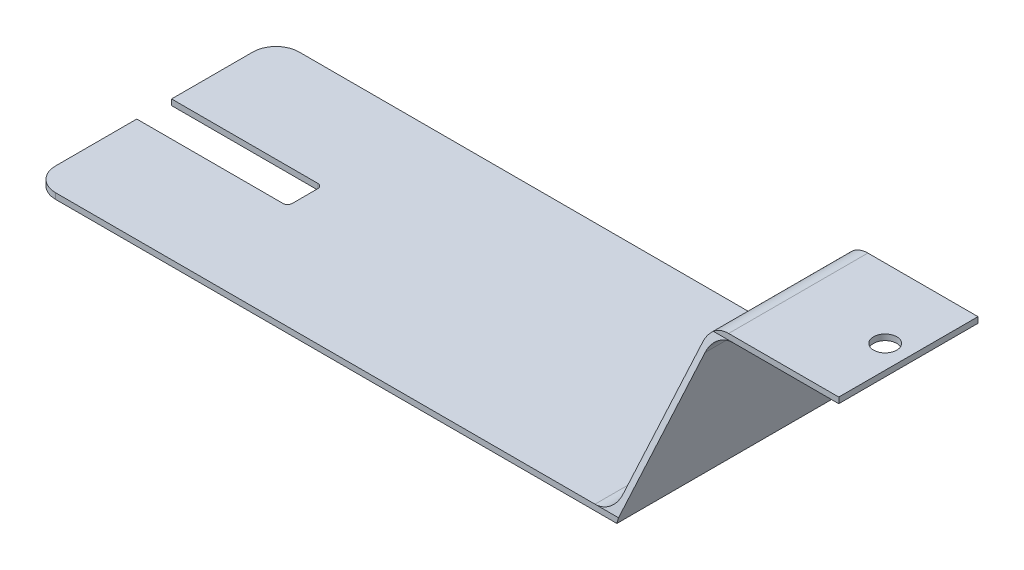
SolidWorks part; units mm, degrees
material "PBT General Purpose"
ref_plane "Front Plane" through (0, 0, 0) normal (0, 0, 1) x (1, 0, 0)
ref_plane "Top Plane" through (0, 0, 0) normal (0, 1, 0) x (1, 0, 0)
ref_plane "Right Plane" through (0, 0, 0) normal (1, 0, 0) x (0, 0, -1)
sketch "Sketch1" plane through (0, 0, 0) normal (0, 0, 1) x (1, 0, 0)
  line L0 (125, 1.25) -> (145, 1.25) construction
  line L1 (-125, -1.25) -> (125, -1.25)
  line L2 (-125, -1.25) -> (-125, 1.25)
  line L3 (-125, 1.25) -> (125, 1.25)
  line L4 (125, -1.25) -> (125, 1.25)
  line L5 (-125, -1.25) -> (125, 1.25) construction
  line L6 (-125, 1.25) -> (125, -1.25) construction
  line L7 (145, 1.25) -> (145, 71.25) construction
  line L8 (125, 1.25) -> (145, 71.25)
  line L9 (146.8858, 68.75) -> (126.8858, -1.25)
  line L10 (125, -1.25) -> (126.8858, -1.25)
  line L11 (145, 71.25) -> (200, 71.25)
  line L12 (200, 71.25) -> (200, 68.75)
  line L13 (200, 68.75) -> (146.8858, 68.75)
  point P0 (0, 0)
  dimension "D1" = 2.5
  dimension "D2" = 250
  dimension "D3" = 20
  dimension "D4" = 70
  dimension "D5" = 2.5
  dimension "D6" = 55
  dimension "D7" = 2.5
extrude "Boss-Extrude1" add sketch "Sketch1" along normal blind 105 contours L1 L10 L9 L13 L12 L11 L8 L3 L2
sketch "Sketch2" plane through (0, 1.25, 0) normal (0, 1, 0) x (1, 0, 0)
  line L0 (-125, -105) -> (-125, 0) construction
  line L1 (-125, -45) -> (-60, -45)
  line L2 (-125, -45) -> (-125, -60)
  line L3 (-125, -60) -> (-60, -60)
  line L4 (-60, -45) -> (-60, -60)
  line L5 (-125, 0) -> (-125, -45) construction
  line L6 (-125, -60) -> (-125, -105) construction
  dimension "D1" = 65
  dimension "D2" = 15
extrude "Cut-Extrude1" cut sketch "Sketch2" against normal up to next
ref_plane "Plane2" through (125, 0, 0) normal (1, 0, 0) x (0, 0, -1)
sketch "Sketch11" plane through (125, 0, 0) normal (1, 0, 0) x (0, 0, -1)
  line L0 (-105, 71.25) -> (0, 71.25) construction
  line L1 (-105, 71.25) -> (0, 71.25) construction
  line L2 (-22.5, 68.75) -> (-82.5, 68.75)
  line L3 (-52.5, 71.25) -> (-52.5, 68.75) construction
  line L4 (-105, 1.25) -> (-82.5, 68.75)
  line L5 (-22.5, 68.75) -> (0, 1.25)
  line L6 (-105, 1.25) -> (-105, 71.25)
  line L7 (-82.5, 68.75) -> (-82.5, 71.25)
  line L8 (-82.5, 71.25) -> (-105, 71.25)
  line L9 (-22.5, 68.75) -> (-22.5, 71.25)
  line L10 (-22.5, 71.25) -> (0, 71.25)
  line L11 (0, 71.25) -> (0, 1.25)
  dimension "D1" = 2.5
  dimension "D2" = 60
extrude "Cut-Extrude12" cut sketch "Sketch11" along normal through all contours L11 L10 L9 L5 | L7 L8 L6 L4 region at (125, 47.8879, 97.2414) region at (125, 47.8879, 7.7586)
sketch "Sketch12" plane through (0, 71.25, 0) normal (0, 1, 0) x (1, 0, 0)
  line L0 (147.5, -82.5) -> (200, -62.5)
  line L1 (200, -82.5) -> (200, -22.5) construction
  line L2 (200, -42.5) -> (200, -62.5)
  line L3 (200, -62.5) -> (200, -82.5)
  line L5 (200, -82.5) -> (147.5, -82.5)
  line L6 (147.5, -22.5) -> (200, -42.5)
  line L7 (200, -22.5) -> (147.5, -22.5)
  line L8 (200, -22.5) -> (200, -42.5)
  line L9 (147.5, -22.5) -> (147.5, -82.5)
  line L10 (200, -22.5) -> (145, -22.5) construction
  line L11 (200, -82.5) -> (145, -82.5) construction
  line L12 (145, -82.5) -> (145, -22.5) construction
  dimension "D1" = 20
  dimension "D2" = 2.5
fillet "Fillet2" radius 10 2 edges at (145, 71.25, 52.5) (146.8858, 68.75, 52.5)
fillet "Fillet3" radius 10 1 edges at (125, 1.25, 52.5)
fillet "Fillet4" radius 2 2 edges at (-60, 0, 45) (-60, 0, 60)
sketch "Sketch13" plane through (0, 71.25, 0) normal (0, 1, 0) x (1, 0, 0)
  line L0 (200, -52.5) -> (190, -52.5) construction
  line L1 (200, -82.5) -> (200, -22.5) construction
  circle A0 centre (190, -52.5) radius 5
  dimension "D1" = 10
  dimension "D2" = 10
extrude "Cut-Extrude15" cut sketch "Sketch13" against normal up to next contours A0
fillet "Fillet5" radius 10 2 edges at (-125, 0, 0) (-125, 0, 105)
